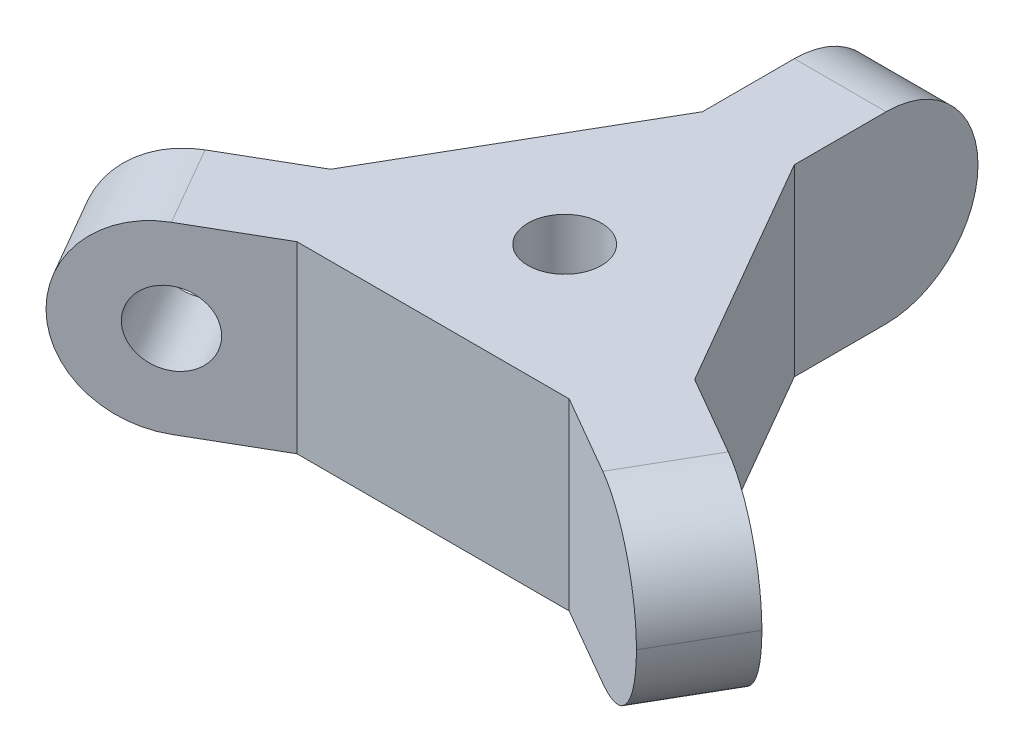
SolidWorks part; units mm, degrees
ref_plane "Front Plane" through (0, 0, 0) normal (0, 0, 1) x (1, 0, 0)
ref_plane "Top Plane" through (0, 0, 0) normal (0, 1, 0) x (1, 0, 0)
ref_plane "Right Plane" through (0, 0, 0) normal (1, 0, 0) x (0, 0, -1)
sketch "Sketch1" plane through (0, 0, 0) normal (0, 1, 0) x (1, 0, 0)
  line L0 (0, 0) -> (0, 6.35) construction
  line L1 (-1.5875, 6.35) -> (1.5875, 6.35)
  line L2 (0, 0) -> (-5.4993, -3.175) construction
  line L3 (0, 0) -> (5.4993, -3.175) construction
  line L4 (-6.293, -1.8002) -> (-4.7055, -4.5498)
  line L5 (4.7055, -4.5498) -> (6.293, -1.8002)
  line L6 (-1.5875, 6.35) -> (-6.293, -1.8002)
  line L7 (-4.7055, -4.5498) -> (4.7055, -4.5498)
  line L8 (6.293, -1.8002) -> (1.5875, 6.35)
  line L9 (-1.5875, 6.35) -> (-1.5875, 12.7)
  line L10 (-1.5875, 12.7) -> (1.5875, 12.7)
  line L11 (1.5875, 12.7) -> (1.5875, 6.35)
  line L12 (-6.293, -1.8002) -> (-11.7923, -4.9752)
  line L13 (-11.7923, -4.9752) -> (-10.2048, -7.7248)
  line L14 (-10.2048, -7.7248) -> (-4.7055, -4.5498)
  line L15 (4.7055, -4.5498) -> (10.2048, -7.7248)
  line L16 (10.2048, -7.7248) -> (11.7923, -4.9752)
  line L17 (11.7923, -4.9752) -> (6.293, -1.8002)
  circle A0 centre (0, 0) radius 1.27
  point P6 (0, 6.35)
  point P13 (5.4993, -3.175)
  point P14 (-5.4993, -3.175)
  point P21 (-11.7923, -4.9752)
  dimension "D1" = 2.54
  dimension "D2" = 6.35
  dimension "D3" = 3.175
  dimension "D4" = 6.35
extrude "Boss-Extrude1" add sketch "Sketch1" along normal blind 6.35 contours L5 L8 L1 L6 L4 L7 A0 | L13 L14 L4 L12 | L16 L17 L5 L15 | L11 L10 L9 L1 region at (0, 0, -9.525) region at (0, 0, -6.1835) region at (-8.2489, 0, 4.7625) region at (8.2489, 0, 4.7625)
sketch "Sketch2" plane through (0.7937, 0, 1.3748) normal (0.5, 0, 0.866) x (0.866, 0, -0.5)
  line L1 (-12.7, 6.35) -> (-6.35, 6.35) construction
  line L2 (-12.7, 6.35) -> (-12.7, 0) construction
  line L3 (-12.7, 0) -> (-6.35, 0) construction
  line L4 (-6.35, 6.35) -> (-6.35, 0) construction
  line L5 (-12.7, 6.35) -> (-6.35, 0) construction
  line L6 (-12.7, 0) -> (-6.35, 6.35) construction
  circle A0 centre (-9.525, 3.175) radius 1.27
  point P4 (-9.525, 3.175)
  dimension "D1" = 2.54
extrude "Cut-Extrude1" cut sketch "Sketch2" against normal up to next
fillet "Fillet1" radius 3.175 6 edges at (0, 6.35, -12.7) (0, 0, -12.7) (10.9985, 0, 6.35) (10.9985, 6.35, 6.35) (-10.9985, 0, 6.35) (-10.9985, 6.35, 6.35)
